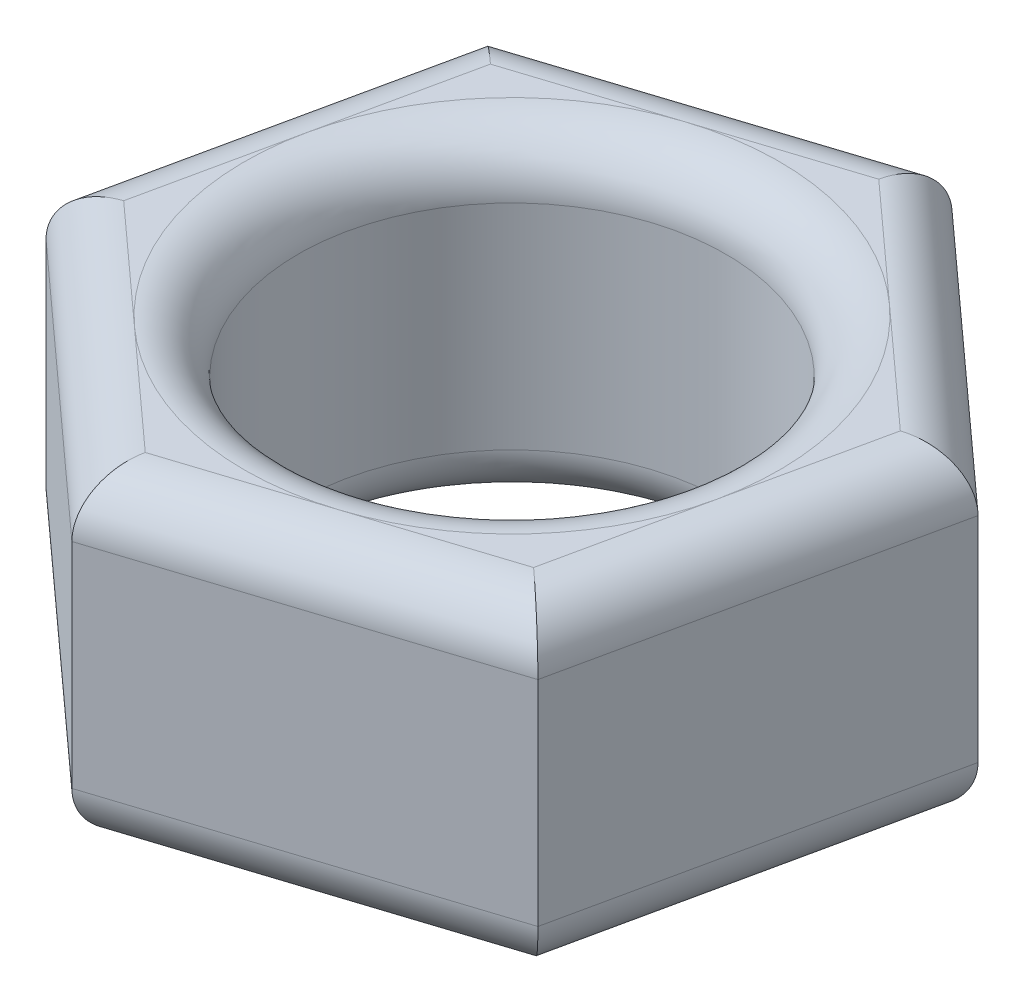
SolidWorks part; units mm, degrees
material "S235JR"
ref_plane "Front Plane" through (0, 0, 0) normal (0, 0, 1) x (1, 0, 0)
ref_plane "Top Plane" through (0, 0, 0) normal (0, 1, 0) x (1, 0, 0)
ref_plane "Right Plane" through (0, 0, 0) normal (1, 0, 0) x (0, 0, -1)
sketch "Sketch1" plane through (0, 0, 0) normal (0, 1, 0) x (1, 0, 0)
  line L1 (-5.1352, 4.6508) -> (-6.5953, -2.1218)
  line L2 (-6.5953, -2.1218) -> (-1.4601, -6.7726)
  line L3 (-1.4601, -6.7726) -> (5.1352, -4.6508)
  line L4 (5.1352, -4.6508) -> (6.5953, 2.1218)
  line L5 (6.5953, 2.1218) -> (1.4601, 6.7726)
  line L6 (1.4601, 6.7726) -> (-5.1352, 4.6508)
  circle A0 centre (0, 0) radius 4
  circle A1 centre (0, 0) radius 6 construction
  dimension "D1" = 8
  dimension "D2" = 12
extrude "Boss-Extrude1" add sketch "Sketch1" along normal blind 6
fillet "Fillet1" radius 1 14 edges at (0, 0, 4) (-1.8375, 0, -5.7117) (-5.8652, 0, -1.2645) (-4.0277, 0, 4.4472) (1.8375, 0, 5.7117) (4.0277, 0, -4.4472) (5.8652, 0, 1.2645) (0, 6, 4) (5.8652, 6, 1.2645) (4.0277, 6, -4.4472) (-1.8375, 6, -5.7117) (-5.8652, 6, -1.2645) (-4.0277, 6, 4.4472) (1.8375, 6, 5.7117)
